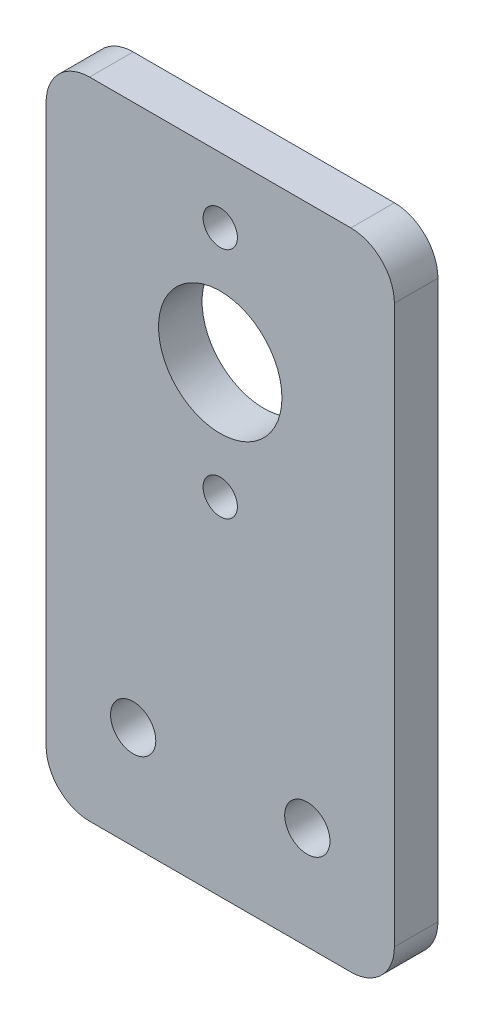
SolidWorks part; units mm, degrees
material "Acrylic (Medium-high impact)"
ref_plane "Front Plane" through (0, 0, 0) normal (0, 0, 1) x (1, 0, 0)
ref_plane "Top Plane" through (0, 0, 0) normal (0, 1, 0) x (1, 0, 0)
ref_plane "Right Plane" through (0, 0, 0) normal (1, 0, 0) x (0, 0, -1)
sketch "Sketch1" plane through (0, 0, 0) normal (0, 0, 1) x (1, 0, 0)
  line L1 (-12.7, -23.5) -> (12.7, -23.5)
  line L2 (-12.7, -23.5) -> (-12.7, 23.5)
  line L3 (-12.7, 23.5) -> (12.7, 23.5)
  line L4 (12.7, -23.5) -> (12.7, 23.5)
  line L5 (-12.7, -23.5) -> (12.7, 23.5) construction
  line L6 (-12.7, 23.5) -> (12.7, -23.5) construction
  point P0 (0, 0)
  dimension "D1" = 25.4
  dimension "D2" = 47
extrude "Boss-Extrude1" add sketch "Sketch1" along normal blind 3.175
sketch "Sketch2" plane through (0, 0, 3.175) normal (0, 0, 1) x (1, 0, 0)
  line L0 (12.7, -23.5) -> (12.7, 23.5) construction
  line L1 (12.7, 23.5) -> (-12.7, 23.5) construction
  circle A0 centre (0, 10.25) radius 4.5
  dimension "D1" = 9
  dimension "D2" = 12.7
  dimension "D3" = 13.25
extrude "Cut-Extrude1" cut sketch "Sketch2" against normal through all
ref_plane "Plane1" through (0, 0, 3.175) normal (0, 0, 1) x (1, 0, 0)
sketch "Sketch3" plane through (0, 0, 3.175) normal (0, 0, 1) x (1, 0, 0)
  line L1 (-12.7, 23.5) -> (-12.7, -23.5) construction
  line L2 (12.7, 23.5) -> (-12.7, 23.5) construction
  point P0 (0, 18.75)
  point P1 (0, 1.75)
  dimension "D1" = 17
  dimension "D2" = 12.7
  dimension "D3" = 4.75
hole_wizard "M3x0.5 Tapped Hole1" positions "Sketch4" profile "Sketch5" tap size "M3x0.5" standard "ANSI Metric" end condition through all
sketch "Sketch4" plane through (0, 0, 3.175) normal (0, 0, 1) x (1, 0, 0)
  point P0 (0, 18.75)
  point P3 (0, 1.75)
sketch "Sketch5" plane through (0, 18.75, 3.175) normal (1, 0, 0) x (0, -1, 0)
  line L0 (0, 0) -> (0, 3.175)
  line L1 (0, 3.175) -> (1.25, 3.175)
  line L2 (1.25, 3.175) -> (1.25, 0)
  line L5 (1.25, 0) -> (0, 0)
  line L11 (0, -6.35) -> (0, 107.95) construction
  dimension "Thru Tap Drill Dia." = 2.5
  dimension "Thru Tap Drill Depth" = 3.175
fillet "Fillet1" radius 3.175 4 edges at (-12.7, -23.5, 1.5875) (12.7, -23.5, 1.5875) (12.7, 23.5, 1.5875) (-12.7, 23.5, 1.5875)
ref_plane "Plane2" through (0, 0, 3.175) normal (0, 0, 1) x (1, 0, 0)
sketch "Sketch6" plane through (0, 0, 3.175) normal (0, 0, 1) x (1, 0, 0)
  line L0 (-12.7, 20.325) -> (-12.7, -20.325) construction
  line L1 (-9.525, -23.5) -> (9.525, -23.5) construction
  point P0 (-6.35, -16)
  point P1 (6.35, -16)
  dimension "D1" = 12.7
  dimension "D2" = 6.35
  dimension "D3" = 7.5
hole_wizard "M4x0.7 Tapped Hole1" positions "Sketch7" profile "Sketch8" tap size "M4x0.7" standard "ANSI Metric" end condition through all
sketch "Sketch7" plane through (0, 0, 3.175) normal (0, 0, 1) x (1, 0, 0)
  point P0 (-6.35, -16)
  point P3 (6.35, -16)
sketch "Sketch8" plane through (-6.35, -16, 3.175) normal (1, 0, 0) x (0, -1, 0)
  line L0 (0, 0) -> (0, 3.175)
  line L1 (0, 3.175) -> (1.65, 3.175)
  line L2 (1.65, 3.175) -> (1.65, 0)
  line L5 (1.65, 0) -> (0, 0)
  line L11 (0, -6.35) -> (0, 107.95) construction
  dimension "Thru Tap Drill Dia." = 3.3
  dimension "Thru Tap Drill Depth" = 3.175
